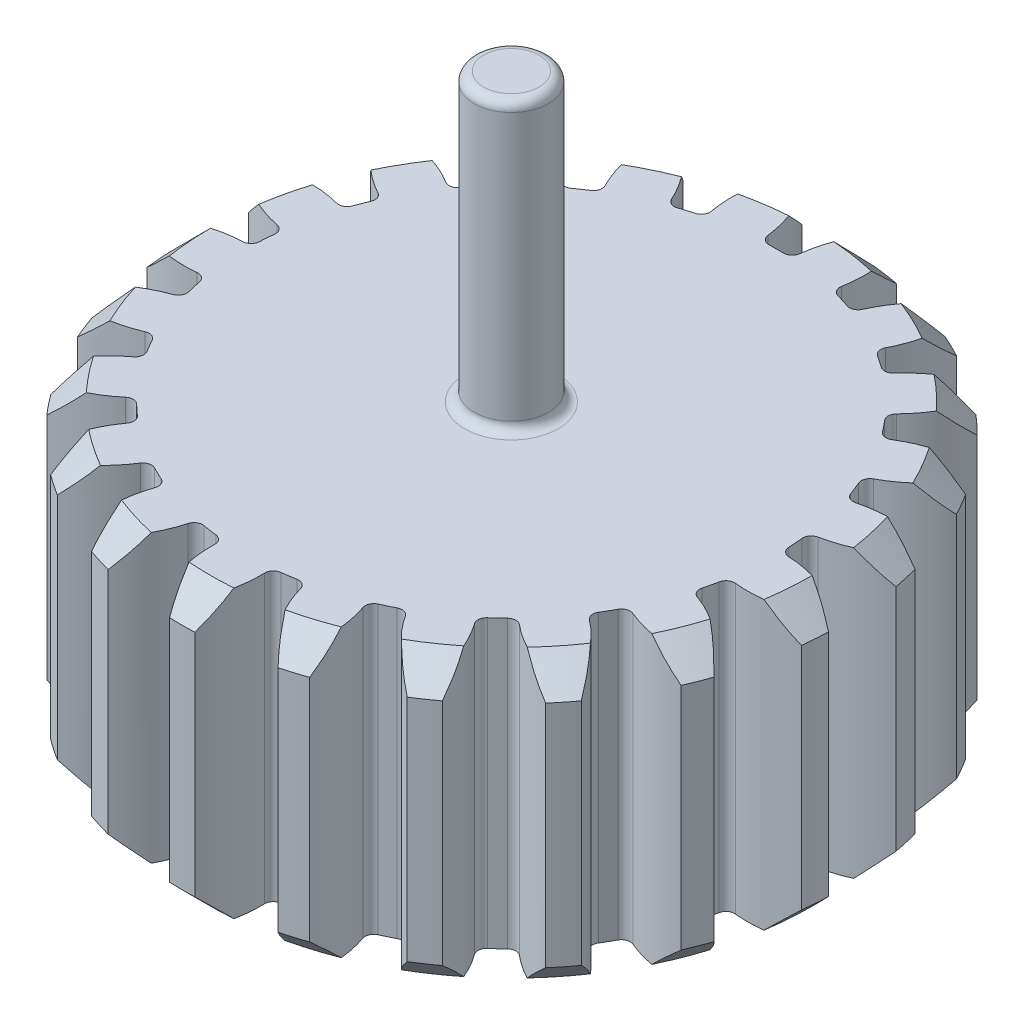
SolidWorks part; units mm, degrees
note: The reader was unsure of these and kept them because the rebuilt part matched: shared geometry of "Esquisse1<4>", "Esquisse1<5>".
material "Nylon 101"
ref_plane "Plan de face" through (0, 0, 0) normal (0, 0, 1) x (1, 0, 0)
ref_plane "Plan de dessus" through (0, 0, 0) normal (0, 1, 0) x (1, 0, 0)
ref_plane "Plan de droite" through (0, 0, 0) normal (1, 0, 0) x (0, 0, -1)
sketch "Esquisse1" plane through (0, 0, 0) normal (0, 1, 0) x (1, 0, 0)
  circle A0 centre (0, 0) radius 15.75 construction
  circle A1 centre (0, 0) radius 17.25
  circle A2 centre (0, 0) radius 1.95
  circle A3 centre (0, 0) radius 5
  dimension "D1" = 31.5
  dimension "D2" = 34.5
  dimension "D3" = 3.9
  dimension "D4" = 10
extrude "Boss.-Extru.1" add sketch "Esquisse1" along normal blind 15 contours A1
sketch "Esquisse2" plane through (0, 0, 0) normal (0, 1, 0) x (1, 0, 0)
  line L0 (0, 0) -> (0, 17.25) construction
  line L1 (0, 0) -> (5.0845, 16.4836) construction
  line L2 (0, 0) -> (2.571, 17.0573) construction
  line L3 (4.8427, 13.0024) -> (0, 0) construction
  line L4 (5.7541, 14.6613) -> (3.5047, 15.3551) construction
  line L5 (3.5047, 15.3551) -> (1.177, 15.706) construction
  line L6 (6.6918, 15.8991) -> (3.6762, 11.9181) construction
  circle A0 centre (0, 0) radius 13.25 construction
  arc A1 (4.8427, 13.0024) -> (3.3233, 13.4711) centre (0, 0) ccw
  circle A2 centre (0, 0) radius 17.25 construction
  circle A3 centre (0, 0) radius 17.25 construction
  arc A4 (6.8816, 15.8179) -> (4.8427, 13.0024) centre (10.9441, 10.73) ccw
  arc A5 (3.2247, 16.9459) -> (3.3233, 13.4711) centre (-2.998, 15.0306) cw
  circle A6 centre (0, 0) radius 15.75 construction
  circle A8 centre (0, 0) radius 17.25 construction
  dimension "D1" = 17.143
  dimension "D2" = 8.571
  dimension "D4" = 3.375
  dimension "D6" = 0.625
  dimension "D5" = 20
extrude "Enlèv. mat.-Extru.1" cut sketch "Esquisse2" against normal through all and the other way through all contours A4 A1 A5
fillet "Congé1" radius 0.45 2 edges at (3.3233, 7.5, -13.4711) (4.8427, 7.5, -13.0024)
chamfer "Chanfrein1" distance 1.5 2 edges at (-5.0845, 15, 16.4836) (-5.0845, 0, 16.4836)
pattern_circular "Répétition circulaire7" count 21 over 360 about axis through (0, 15, 0) along (0, -1, 0) of "Enlèv. mat.-Extru.1"
fillet "Congé2" radius 0.45 40 edges at (13.328, 7.5, 3.8575) (13.6818, 7.5, 2.3073) (13.8729, 7.5, -0.2424) (13.7541, 7.5, -1.828) (13.1851, 7.5, -4.3207) (12.6042, 7.5, -5.8009) (11.3258, 7.5, -8.0151) (10.3344, 7.5, -9.2583) (8.4601, 7.5, -10.9974) (7.1463, 7.5, -11.8931) (-12.6042, 7.5, -5.8009) (-13.1851, 7.5, -4.3207) (-13.7541, 7.5, -1.828) (-13.8729, 7.5, -0.2424) (-13.6818, 7.5, 2.3073) (-13.328, 7.5, 3.8575) (-12.3939, 7.5, 6.2376) (-11.5988, 7.5, 7.6146) (-10.0047, 7.5, 9.6136) (-8.8391, 7.5, 10.6952) (-6.7266, 7.5, 12.1354) (-5.2939, 7.5, 12.8254) (-2.8507, 7.5, 13.579) (-1.2784, 7.5, 13.816) (1.2784, 7.5, 13.816) (2.8507, 7.5, 13.579) (5.2939, 7.5, 12.8254) (6.7266, 7.5, 12.1354) (8.8391, 7.5, 10.6952) (10.0047, 7.5, 9.6136) (11.5988, 7.5, 7.6146) (12.3939, 7.5, 6.2376) (0.795, 7.5, -13.8522) (-0.795, 7.5, -13.8522) (-3.3233, 7.5, -13.4711) (-4.8427, 7.5, -13.0024) (-7.1463, 7.5, -11.8931) (-8.4601, 7.5, -10.9974) (-10.3344, 7.5, -9.2583) (-11.3258, 7.5, -8.0151)
extrude "Boss.-Extru.2" add sketch "Esquisse1<4>" along normal blind 30 contours A2
sketch "Esquisse1<4>" plane through (0, 0, 0) normal (0, 1, 0) x (1, 0, 0) same geometry as "Esquisse1"
fillet "Congé4" radius 0.5 1 edges at (0, 30, 1.95)
fillet "Congé5" radius 0.5 1 edges at (0, 15, 1.95)
extrude "Enlèv. mat.-Extru.2" cut sketch "Esquisse1<5>" along normal blind 10 contours A3
sketch "Esquisse1<5>" plane through (0, 0, 0) normal (0, 1, 0) x (1, 0, 0) same geometry as "Esquisse1"
equation "\"Module\"= 1.5mm"
equation "\"Number of teeth\"= 21"
equation "\"Pressure Angle\"=20"
equation "\"D1@Esquisse1\"=\"Module\"*\"Number of teeth\""
equation "\"D2@Esquisse1\"=(\"Number of teeth\"+2) * \"Module\""
equation "\"D1@Esquisse2\"=360/ \"Number of teeth\""
equation "\"D2@Esquisse2\"=\"D1@Esquisse2\"/2"
equation "\"D4@Esquisse2\"=\"Module\" * if( \"Module\"=>1.25,2.25,2.4)"
equation "\"D5@Esquisse2\"=\"Pressure Angle\""
equation "\"D1@Congé1\"=0.3* \"Module\""
equation "\"D1@Répétition circulaire7\"=\"Number of teeth\""
equation "\"D1@Congé3\"=\"Module\""
equation "\"D1@Chanfrein1\"=\"Module\""
equation "\"D1@Congé2\"=0.3* \"Module\""
